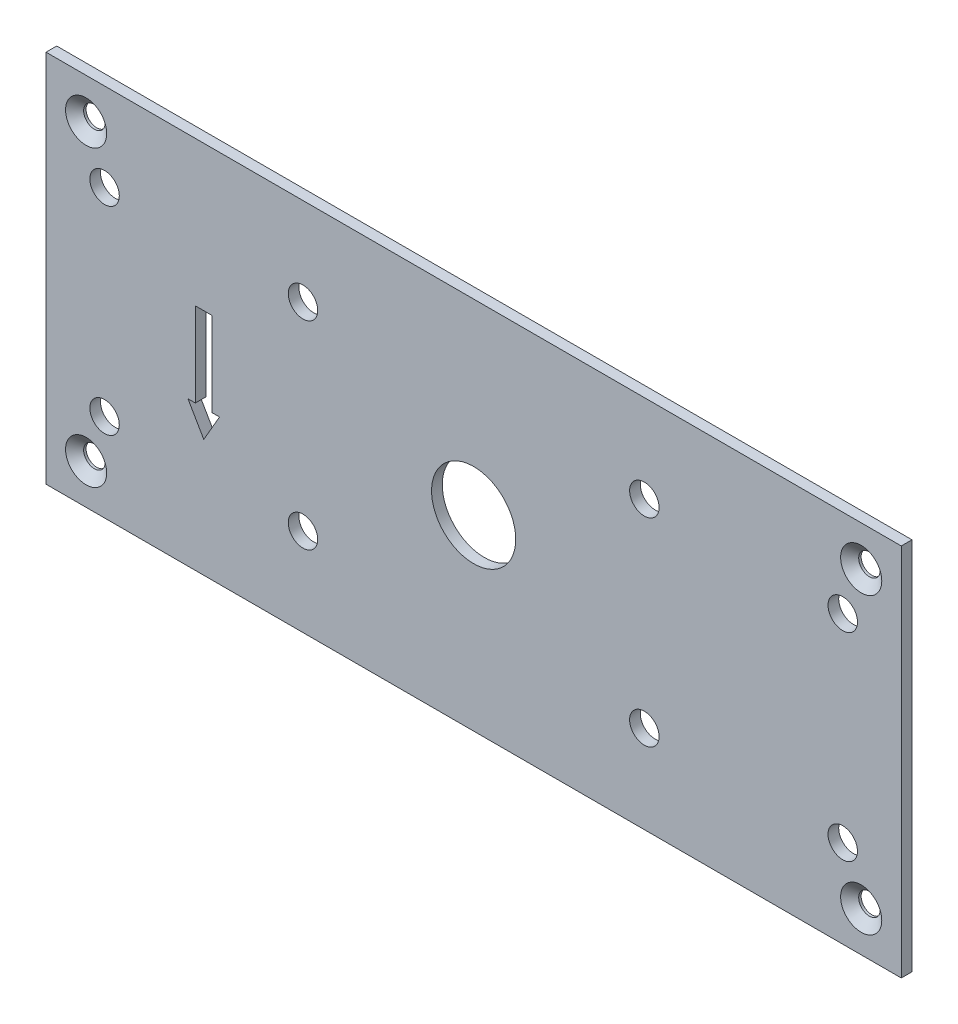
SolidWorks part; units mm, degrees
ref_plane "Front Plane" through (0, 0, 0) normal (0, 0, 1) x (1, 0, 0)
ref_plane "Top Plane" through (0, 0, 0) normal (0, 1, 0) x (1, 0, 0)
ref_plane "Right Plane" through (0, 0, 0) normal (1, 0, 0) x (0, 0, -1)
sketch "Sketch2" plane through (0, 0, 0) normal (0, 0, 1) x (1, 0, 0)
  line L0 (-40.555, 23.57) -> (-87.695, 23.57) construction
  line L1 (-101.6, -44.45) -> (101.6, -44.45)
  line L2 (-101.6, -44.45) -> (-101.6, 44.45)
  line L3 (-101.6, 44.45) -> (101.6, 44.45)
  line L4 (101.6, -44.45) -> (101.6, 44.45)
  line L5 (-101.6, -44.45) -> (101.6, 44.45) construction
  line L6 (-101.6, 44.45) -> (101.6, -44.45) construction
  line L7 (-87.695, 23.57) -> (-87.695, -23.57) construction
  line L8 (-87.695, -23.57) -> (-40.555, -23.57) construction
  line L9 (-40.555, -23.57) -> (-40.555, 23.57) construction
  line L10 (0, 0) -> (-64.125, 0) construction
  line L11 (0, 0) -> (64.125, 0) construction
  line L12 (40.555, -23.57) -> (87.695, -23.57) construction
  line L13 (87.695, -23.57) -> (87.695, 23.57) construction
  line L14 (87.695, 23.57) -> (40.555, 23.57) construction
  line L15 (40.555, 23.57) -> (40.555, -23.57) construction
  circle A11 centre (-87.695, 23.57) radius 3.5
  circle A12 centre (-40.555, 23.57) radius 3.5
  circle A13 centre (-40.555, -23.57) radius 3.5
  circle A14 centre (-87.695, -23.57) radius 3.5
  circle A15 centre (40.555, -23.57) radius 3.5
  circle A16 centre (87.695, -23.57) radius 3.5
  circle A17 centre (87.695, 23.57) radius 3.5
  circle A18 centre (40.555, 23.57) radius 3.5
  circle A19 centre (0, 0) radius 10
  point P0 (0, 0)
  point P15 (0, 0)
  point P28 (-64.125, 23.57)
  point P29 (64.125, 23.57)
  dimension "D3" = 7
  dimension "D6" = 20
  dimension "D1" = 47.14
  dimension "D2" = 88.9
  dimension "D4" = 203.2
  dimension "D5" = 64.125
extrude "Boss-Extrude1" add sketch "Sketch2" along normal mid plane 2.54
sketch "Sketch3" plane through (0, 0, 1.27) normal (0, 0, 1) x (1, 0, 0)
  line L0 (-101.6, 34.925) -> (-92.075, 34.925) construction
  line L1 (-101.6, 44.45) -> (-101.6, -44.45) construction
  line L2 (-92.075, 34.925) -> (-92.075, 44.45) construction
  line L3 (101.6, 44.45) -> (-101.6, 44.45) construction
  line L4 (92.075, 44.45) -> (92.075, 34.925) construction
  line L5 (92.075, 34.925) -> (101.6, 34.925) construction
  line L6 (101.6, -44.45) -> (101.6, 44.45) construction
  line L7 (92.075, -44.45) -> (92.075, -34.925) construction
  line L8 (-101.6, -44.45) -> (101.6, -44.45) construction
  line L9 (92.075, -34.925) -> (101.6, -34.925) construction
  line L10 (-92.075, -44.45) -> (-92.075, -34.925) construction
  line L11 (-92.075, -34.925) -> (-101.6, -34.925) construction
  circle A0 centre (-92.075, 34.925) radius 2.5527
  circle A1 centre (-92.075, -34.925) radius 2.5527
  circle A2 centre (92.075, -34.925) radius 2.5527
  circle A3 centre (92.075, 34.925) radius 2.5527
  dimension "D2" = 5.1054
  dimension "D1" = 9.525
extrude "Cut-Extrude1" cut sketch "Sketch3" against normal through all
sketch "Sketch4" plane through (0, 0, 1.27) normal (0, 0, 1) x (1, 0, 0)
  line L0 (-87.695, 23.57) -> (-40.555, -23.57) construction
  line L1 (-66.125, -10) -> (-67.8747, -10)
  line L2 (-66.125, -10) -> (-62.125, -10)
  line L3 (-66.125, -10) -> (-66.125, 10)
  line L4 (-66.125, 10) -> (-62.125, 10)
  line L5 (-62.125, -10) -> (-62.125, 10)
  line L6 (-66.125, -10) -> (-62.125, 10) construction
  line L7 (-66.125, 10) -> (-62.125, -10) construction
  line L8 (-67.8747, -10) -> (-64.125, -16.4946)
  line L9 (-64.125, -16.4946) -> (-60.3753, -10)
  line L10 (-62.125, -10) -> (-60.3753, -10)
  point P3 (-64.125, 0)
  dimension "D1" = 4
  dimension "D2" = 20
  dimension "D3" = 60
extrude "Cut-Extrude2" cut sketch "Sketch4" against normal through all both and the other way through all contours L10 L2 L1 L8 L9 | L2 L5 L4 L3 region at (-64.125, -12.1649, 1.27) region at (-64.125, 0, 1.27)
hole_wizard "CSK for #10 Flat Head Machine Screw (100)1" positions "Sketch5" profile "Sketch6" countersink size "#10" standard "ANSI Inch" end condition through all
sketch "Sketch5" plane through (0, 0, 1.27) normal (0, 0, 1) x (1, 0, 0)
  point P0 (-92.075, 34.925)
  point P3 (-92.075, -34.925)
  point P6 (92.075, -34.925)
  point P9 (92.075, 34.925)
sketch "Sketch6" plane through (-92.075, 34.925, 1.27) normal (1, 0, 0) x (0, -1, 0)
  line L0 (0, 0) -> (0, 2.54)
  line L1 (0, 2.54) -> (2.5527, 2.54)
  line L2 (2.5527, 2.54) -> (2.5527, 1.9608)
  line L3 (2.5527, 1.9608) -> (4.8895, 0)
  line L5 (4.8895, 0) -> (0, 0)
  line L6 (-2.5527, 1.9608) -> (-4.8895, 0) construction
  line L11 (0, -6.35) -> (0, 107.95) construction
  dimension "Thru Hole Dia." = 5.1054
  dimension "Thru Hole Depth" = 2.54
  dimension "Near C'Sink Dia." = 9.779
  dimension "Near C'Sink Angle" = 100
